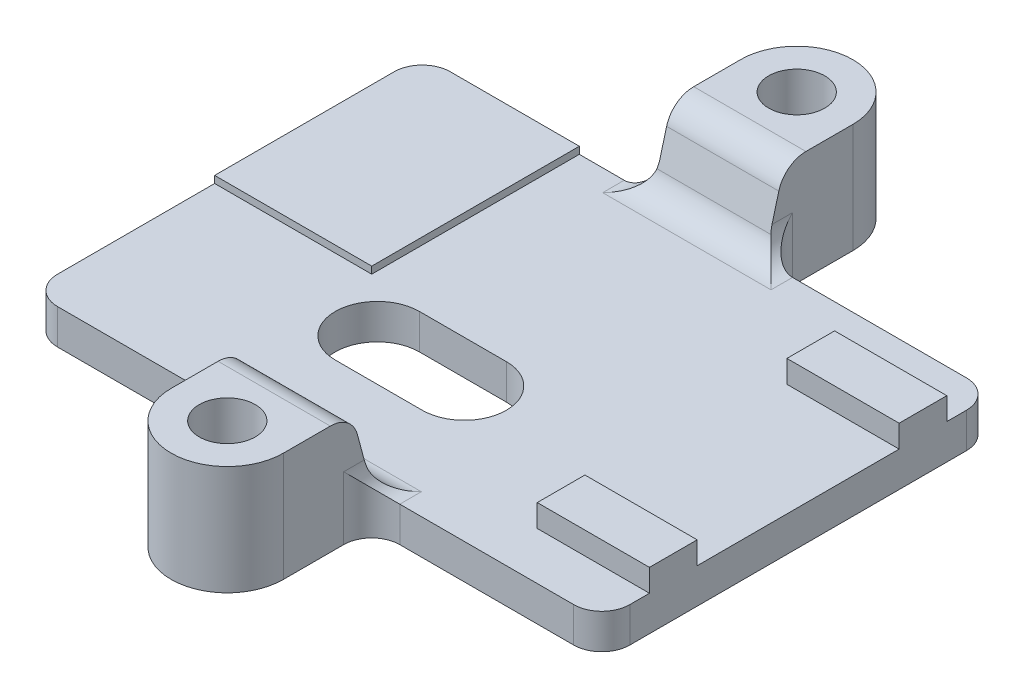
SolidWorks part; units mm, degrees
ref_plane "Plane XZ" through (0, 0, 0) normal (0, 0, 1) x (1, 0, 0)
ref_plane "Plane XY" through (0, 0, 0) normal (0, 1, 0) x (1, 0, 0)
ref_plane "Plane YZ" through (0, 0, 0) normal (1, 0, 0) x (0, 0, -1)
sketch "Sketch1" plane through (0, 0, 0) normal (0, 1, 0) x (1, 0, 0)
  line L0 (-10.414, 0) -> (10.414, 0) construction
  line L1 (-10.414, 8.89) -> (10.414, 8.89) construction
  line L2 (-10.414, 8.89) -> (-10.414, -8.89) construction
  line L3 (-10.414, -8.89) -> (10.414, -8.89) construction
  line L4 (10.414, 8.89) -> (10.414, -8.89) construction
  line L10 (-12.954, -8.89) -> (12.954, -8.89)
  line L11 (-12.954, -8.89) -> (-12.954, 8.89)
  line L12 (-12.954, 8.89) -> (12.954, 8.89)
  line L13 (12.954, -8.89) -> (12.954, 8.89)
  dimension "D1" = 20.828
  dimension "D2" = 17.78
  dimension "D3" = 2.54
  dimension "D4" = 2.54
extrude "Boss-Extrude1" add sketch "Sketch1" along normal blind 1.5875
sketch "Sketch2" plane through (0, 1.5875, 0) normal (0, 1, 0) x (1, 0, 0)
  line L1 (12.954, -4.572) -> (7.874, -4.572)
  line L2 (12.954, -4.572) -> (12.954, -6.731)
  line L3 (12.954, -6.731) -> (7.874, -6.731)
  line L4 (7.874, -4.572) -> (7.874, -6.731)
  line L5 (12.954, 4.572) -> (12.954, -4.572) construction
  line L6 (12.954, 4.572) -> (7.874, 4.572)
  line L7 (12.954, 4.572) -> (12.954, 6.731)
  line L8 (12.954, 6.731) -> (7.874, 6.731)
  line L9 (7.874, 4.572) -> (7.874, 6.731)
  line L10 (0, 0) -> (12.954, 0) construction
  line L11 (12.954, -8.89) -> (12.954, 8.89) construction
  dimension "D1" = 9.144
  dimension "D2" = 2.159
  dimension "D3" = 5.08
extrude "Boss-Extrude2" add sketch "Sketch2" along normal blind 1.016
sketch "Sketch3" plane through (0, 1.5875, 0) normal (0, 1, 0) x (1, 0, 0)
  line L1 (-12.954, -0.508) -> (-5.842, -0.508)
  line L2 (-12.954, -0.508) -> (-12.954, 8.89)
  line L3 (-12.954, 8.89) -> (-5.842, 8.89)
  line L4 (-5.842, -0.508) -> (-5.842, 8.89)
  dimension "D1" = 9.398
  dimension "D2" = 7.112
extrude "Boss-Extrude3" add sketch "Sketch3" along normal blind 0.3175
sketch "Sketch4" plane through (0, 0, 0) normal (0, -1, 0) x (1, 0, 0)
  line L0 (0, 12.8905) -> (0, 8.89) construction
  line L1 (-10.414, 8.89) -> (10.414, 8.89) construction
  line L2 (-10.414, 0) -> (10.414, 0) construction
  line L3 (-10.414, 0) -> (10.414, 0) construction
  line L4 (2.54, 12.8905) -> (2.54, 8.89)
  line L5 (-12.954, 8.89) -> (12.954, 8.89) construction
  line L6 (2.54, 8.89) -> (-2.54, 8.89)
  line L7 (-2.54, 8.89) -> (-2.54, 12.8905)
  line L8 (2.54, -12.8905) -> (2.54, -8.89)
  line L9 (2.54, -8.89) -> (-2.54, -8.89)
  line L10 (-2.54, -8.89) -> (-2.54, -12.8905)
  circle A0 centre (0, 12.8905) radius 2.54 construction
  arc A1 (2.54, 12.8905) -> (-2.54, 12.8905) centre (0, 12.8905) ccw
  circle A2 centre (0, 12.8905) radius 1.27
  circle A3 centre (0, -12.8905) radius 1.27
  arc A4 (2.54, -12.8905) -> (-2.54, -12.8905) centre (0, -12.8905) cw
  dimension "D1" = 5.08
  dimension "D3" = 2.54
  dimension "D2" = 25.781
extrude "Boss-Extrude4" add sketch "Sketch4" against normal blind 4.953
sketch "Sketch5" plane through (0, 0, 0) normal (0, -1, 0) x (1, 0, 0)
  line L0 (-3.302, 2.794) -> (0.635, 2.794) construction
  line L1 (-3.302, 4.699) -> (0.635, 4.699)
  line L2 (-3.302, 0.889) -> (0.635, 0.889)
  line L3 (-12.954, 8.89) -> (12.954, 8.89) construction
  line L5 (-10.414, -8.89) -> (-10.414, 8.89) construction
  arc A0 (-3.302, 4.699) -> (-3.302, 0.889) centre (-3.302, 2.794) ccw
  arc A1 (0.635, 0.889) -> (0.635, 4.699) centre (0.635, 2.794) ccw
  point P2 (-1.3335, 2.794)
  dimension "D4" = 1.905
  dimension "D1" = 6.096
  dimension "D2" = 7.112
  dimension "D3" = 11.049
extrude "Cut-Extrude1" cut sketch "Sketch5" against normal through all
chamfer "Chamfer1" distance 3.3655 angle 15 2 edges at (0, 4.953, -8.89) (0, 4.953, 8.89) first distance on face at (0, 3.2702, -8.89) first distance on face at (0, 3.2702, 8.89)
fillet "Fillet1" radius 1.27 4 edges at (0, 4.953, -9.7918) (0, 4.953, 9.7918) (0, 1.5875, 8.89) (0, 1.5875, -8.89)
fillet "Fillet3" radius 1.27 4 edges at (-2.54, 0.7937, 8.89) (2.54, 0.7937, 8.89) (-2.54, 0.7937, -8.89) (2.54, 0.7937, -8.89)
fillet "Fillet4" radius 1.27 4 edges at (2.54, 1.5875, 9.0377) (-2.54, 1.5875, 9.0377) (2.54, 1.5875, -9.0377) (-2.54, 1.5875, -9.0377)
fillet "Fillet5" radius 1.27 4 edges at (-12.954, 0.9525, -8.89) (-12.954, 0.7937, 8.89) (12.954, 0.7937, 8.89) (12.954, 0.7937, -8.89)
